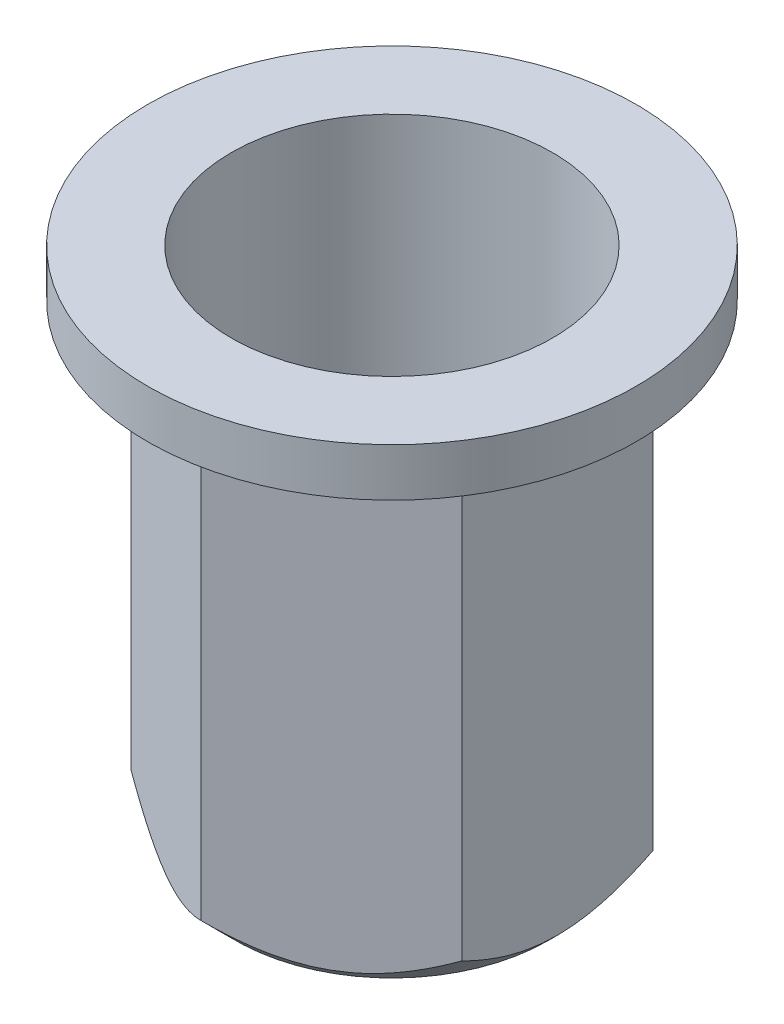
SolidWorks part; units mm, degrees
ref_plane "Front Plane" through (0, 0, 0) normal (0, 0, 1) x (1, 0, 0)
ref_plane "Top Plane" through (0, 0, 0) normal (0, 1, 0) x (1, 0, 0)
ref_plane "Right Plane" through (0, 0, 0) normal (1, 0, 0) x (0, 0, -1)
sketch "Sketch1" plane through (0, 0, 0) normal (0, 0, 1) x (1, 0, 0)
  line L0 (-4.3408, -11.1189) -> (-3.547, -11.9126)
  line L1 (-3.6512, -5.5626) -> (-2.3813, -5.5626) construction
  line L2 (-2.3813, -5.5626) -> (-2.3813, -6.8326) construction
  line L3 (-3.547, -11.9126) -> (-3.175, -11.9126)
  line L5 (-3.175, -11.9126) -> (-2.3812, -11.1189)
  line L6 (4.3408, 0) -> (2.1704, 3.7592) construction
  line L7 (-2.3812, -11.1189) -> (-2.3813, -6.8326)
  line L8 (4.3408, -11.9126) -> (3.547, -11.9126) construction
  line L9 (-2.3813, -6.8326) -> (-3.6512, -5.5626)
  line L10 (2.3813, -11.9126) -> (2.3813, -11.1189) construction
  line L11 (-3.6512, -5.5626) -> (-3.6512, 0)
  line L12 (4.3408, -11.1188) -> (4.3408, -11.9126) construction
  line L13 (3.175, -11.9126) -> (2.3813, -11.9126) construction
  line L14 (-3.6512, 0) -> (-5.5499, 0)
  line L15 (2.1704, 3.7592) -> (-2.1704, 3.7592) construction
  line L16 (5.5499, -9.6012) -> (5.5499, -3.2512) construction
  line L17 (-5.5499, 0) -> (-5.5499, -1.0922)
  line L18 (5.5499, -1.0922) -> (4.3408, -1.0922) construction
  line L19 (-5.5499, -1.0922) -> (-4.3408, -1.0922)
  line L20 (-4.3408, -1.0922) -> (-4.3408, -11.1189)
  line L21 (0, 0) -> (0, -11.9126) construction
  line L22 (-2.1704, 3.7592) -> (-4.3408, 0) construction
  line L23 (-4.3408, 0) -> (-2.1704, -3.7592) construction
  line L24 (-4.3408, -11.1189) -> (-4.3408, -11.9126) construction
  line L25 (-4.3408, -11.9126) -> (-3.547, -11.9126) construction
  line L26 (-3.175, -11.9126) -> (-2.3812, -11.9126) construction
  line L27 (-2.3812, -11.9126) -> (-2.3812, -11.1189) construction
  line L28 (-2.3812, -11.9126) -> (0, -11.9126) construction
  line L29 (5.5499, 0) -> (5.5499, -1.0922) construction
  line L30 (-3.547, -11.9126) -> (-2.3812, -11.9126) construction
  line L31 (-2.1704, -3.7592) -> (2.1704, -3.7592) construction
  line L32 (0, 0) -> (-3.6512, 0) construction
  line L33 (2.1704, -3.7592) -> (4.3408, 0) construction
  circle A0 centre (0, 0) radius 3.7592 construction
  point P1 (-3.7592, 0)
  dimension "D7" = 4.7625
  dimension "D8" = 45
  dimension "D12" = 6.35
  dimension "D2" = 7.3025
revolve "Revolve1" add sketch "Sketch1" angle 360 about L21
sketch "Sketch2" plane through (0, -11.9126, 0) normal (0, -1, 0) x (1, 0, 0)
  circle A1 centre (0, 0) radius 3.175
  point P1 (3.175, 0)
  dimension "D1" = 6.35
ref_plane "Plane1" through (-4.3408, 0, 0) normal (1, 0, 0) x (0, 0, -1)
curve "Helix/Spiral1" pitch 1.27 height 19.3446 radius 3.175 centre (0, -11.9126, 0) axis (0, 1, 0) start towards (1, 0, 0) parameters "Height"=19.3446, "Pitch"=1.27
sketch "Sketch3" plane through (0, 0, 0) normal (0, 0, 1) x (1, 0, 0)
  line L0 (2.2126, -11.357) -> (2.2126, -12.627) construction
  line L1 (2.2126, -12.627) -> (3.3125, -11.992) construction
  line L2 (2.2126, -11.357) -> (3.3125, -11.992) construction
  line L3 (2.3501, -11.4363) -> (2.3501, -12.5476) construction
  line L6 (2.2126, -11.992) -> (2.3501, -11.992) construction
  line L8 (3.175, -11.992) -> (3.3125, -11.992) construction
  line L9 (3.175, -11.9126) -> (3.175, -12.0713) construction
  line L11 (2.2814, -11.3967) -> (2.2814, -12.5873)
  line L12 (2.2814, -12.5873) -> (3.175, -12.0713)
  line L14 (3.175, -11.9126) -> (2.2814, -11.3967)
  arc A0 (3.175, -12.0713) -> (3.175, -11.9126) centre (3.1292, -11.992) ccw
  point P13 (2.2814, -11.992)
  dimension "D1" = 1.27
  dimension "D2" = 0.1588
sweep "Cut-Sweep1" cut profiles "Sketch3" path "Helix/Spiral1" align with end faces yes
sketch "Sketch4" plane through (0, -1.0922, 0) normal (0, -1, 0) x (1, 0, 0)
  line L1 (0, 4.3408) -> (-3.7592, 2.1704)
  line L2 (-3.7592, 2.1704) -> (-3.7592, -2.1704)
  line L3 (-3.7592, -2.1704) -> (0, -4.3408)
  line L4 (0, -4.3408) -> (3.7592, -2.1704)
  line L5 (3.7592, -2.1704) -> (3.7592, 2.1704)
  line L6 (3.7592, 2.1704) -> (0, 4.3408)
  circle A0 centre (0, 0) radius 3.7592 construction
extrude "Extrude2" cut sketch "Sketch4" along normal through all flip side to cut
ref_plane "Plane2" [suppressed] through (0, -1.6002, 0) normal (0, -1, 0) x (1, 0, 0)
sketch "Sketch5" [suppressed] plane through (0, -1.6002, 0) normal (0, -1, 0) x (1, 0, 0)
  circle A0 centre (0, 0) radius 4.3408
  point P3 (-4.3408, 0)
extrude "Extrude3" [suppressed] cut sketch "Sketch5" along normal blind 2.3114
pattern_linear "LPattern1" [suppressed] count 2 spacing 2.3114 along (0, 1, 0) of bodies 124 117
delete or keep bodies "Body-Delete1" [suppressed] type delete bodies bodies 124
combine bodies "Combine1" [suppressed] operation type add bodies to combine 123 119
sketch "Sketch6" [suppressed] plane through (0, 0, 0) normal (0, 0, 1) x (1, 0, 0)
  line L0 (-4.3408, -1.6002) -> (-3.6512, -1.6002)
  line L1 (-3.6512, -1.6002) -> (-3.6512, -3.1242)
  line L2 (-3.6512, -3.1242) -> (-4.3408, -3.1242)
  line L3 (-3.6512, -3.9624) -> (-3.6512, 0) construction
  line L4 (-6.985, -1.6002) -> (6.985, -1.6002) construction
  line L5 (-4.3408, -1.0922) -> (-4.3408, -9.5186) construction
  line L6 (0, 0) -> (0, -10.3124) construction
  line L7 (0, 0) -> (0, -10.3124) construction
  arc A0 (-4.3408, -1.6002) -> (-4.3408, -3.1242) centre (-4.3408, -2.3622) ccw
  dimension "D1" = 1.524
revolve "Revolve2" [suppressed] add sketch "Sketch6" angle 360 about L7
equation "\"Height@Helix/Spiral1\" = \"Body Lg@Sketch1\" + \"Pitch@Helix/Spiral1\" +  (  pi  / 11 ) "
equation "\"D1@Sketch3\" = \"Pitch@Helix/Spiral1\""
equation "\"D2@Sketch3\" = \"D1@Sketch3\" / 8"
equation "\"D1@Extrude3\" = \"D1@Sketch1\""
equation "\"D3@LPattern1\" = \"D1@Extrude3\""
equation "\"D7@Sketch1\" = \"Thread Dia@Sketch1\" -  ( \"Pitch@Helix/Spiral1\" )  * 1.25"
equation "\"D2@Sketch1\" =  \"Thread Dia@Sketch1\" + ( \"Pitch@Helix/Spiral1\" * 6 / 8 )"
equation "\"D12@Sketch1\" = \"Max Installed Lg@Sketch1\""
equation "\"D1@Sketch2\" = \"Thread Dia@Sketch1\""
